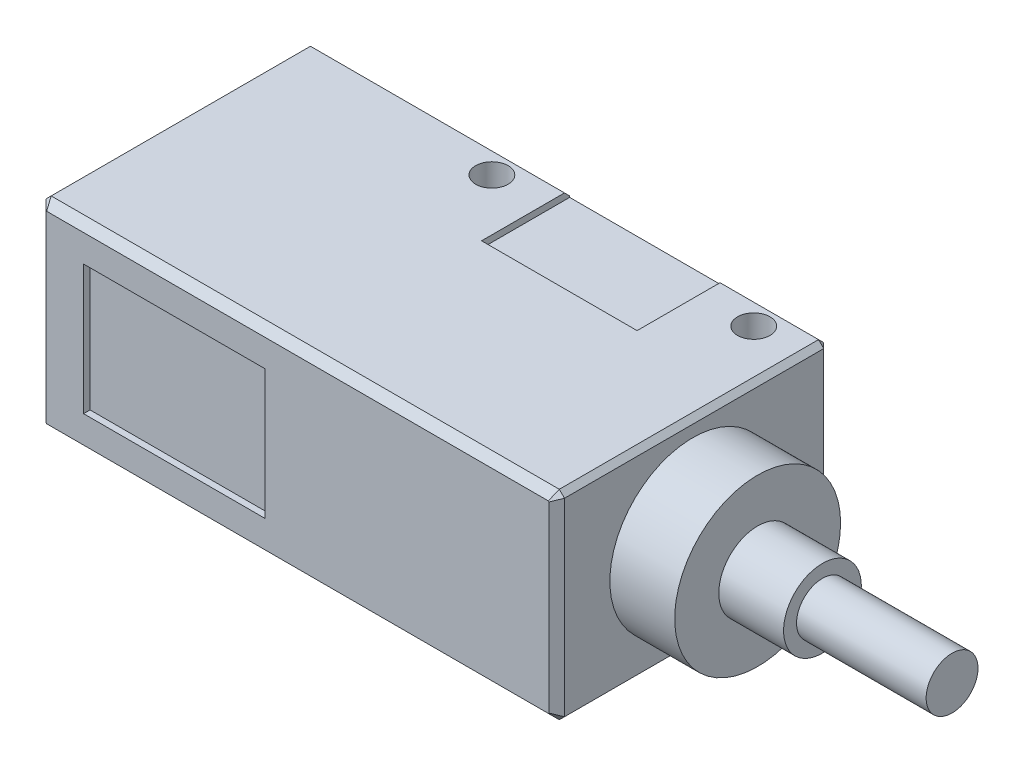
SolidWorks part; units mm, degrees
material "ABS"
ref_plane "Front Plane" through (0, 0, 0) normal (0, 0, 1) x (1, 0, 0)
ref_plane "Top Plane" through (0, 0, 0) normal (0, 1, 0) x (1, 0, 0)
ref_plane "Right Plane" through (0, 0, 0) normal (1, 0, 0) x (0, 0, -1)
sketch "Sketch1" plane through (0, 0, 0) normal (1, 0, 0) x (0, 0, -1)
  line L1 (-10.5, 7.7) -> (10.5, 7.7)
  line L2 (-10.5, 7.7) -> (-10.5, -7.7)
  line L3 (-10.5, -7.7) -> (10.5, -7.7)
  line L4 (10.5, 7.7) -> (10.5, -7.7)
  line L5 (-10.5, 7.7) -> (10.5, -7.7) construction
  line L6 (-10.5, -7.7) -> (10.5, 7.7) construction
  point P0 (0, 0)
  dimension "D1" = 21
  dimension "D2" = 15.4
extrude "Boss-Extrude1" add sketch "Sketch1" along normal blind 40
sketch "Sketch2" plane through (0, 0, 10.5) normal (0, 0, 1) x (1, 0, 0)
  line L0 (40, 7.7) -> (40, -7.7) construction
  line L1 (3.5, 5) -> (17.5, 5)
  line L2 (3.5, 5) -> (3.5, -5)
  line L3 (3.5, -5) -> (17.5, -5)
  line L4 (17.5, 5) -> (17.5, -5)
  line L5 (3.5, 5) -> (17.5, -5) construction
  line L6 (3.5, -5) -> (17.5, 5) construction
  line L10 (0, 0) -> (40, 0) construction
  point P0 (10.5, 0)
  dimension "D1" = 29.5
  dimension "D2" = 7
  dimension "D3" = 10
extrude "Cut-Extrude1" cut sketch "Sketch2" against normal blind 0.5
sketch "Sketch3" plane through (0, 7.7, 0) normal (0, 1, 0) x (1, 0, 0)
  line L0 (40, 10.5) -> (0, 10.5) construction
  line L1 (20, 10.5) -> (32, 10.5)
  line L2 (20, 10.5) -> (20, 3.7)
  line L3 (20, 3.7) -> (32, 3.7)
  line L4 (32, 10.5) -> (32, 3.7)
  line L5 (0, 10.5) -> (0, -10.5) construction
  dimension "D1" = 20
  dimension "D2" = 12
  dimension "D3" = 6.8
extrude "Cut-Extrude2" cut sketch "Sketch3" against normal blind 0.5
extrude "Cut-Extrude3" cut sketch "Sketch3<2>" along normal blind 0.5 from surface starting at face at (20, -7.7, 0)
sketch "Sketch3<2>" plane through (0, 7.7, 0) normal (0, 1, 0) x (1, 0, 0) same geometry as "Sketch3"
hole_wizard "M3 Tapped Hole1" positions "Sketch5" profile "Sketch4" tap size "M3" standard "ISO" end condition up to next
sketch "Sketch5" plane through (0, 7.7, 0) normal (0, 1, 0) x (-1, 0, 0)
  line L0 (-40, -10.5) -> (-32, -10.5) construction
  line L1 (-40, -10.5) -> (-40, 10.5) construction
  point P0 (-36.2, -8.5)
  dimension "D1" = 2
  dimension "D2" = 3.8
sketch "Sketch4" plane through (36.2, 7.7, -8.5) normal (1, 0, 0) x (0, 0, 1)
  line L0 (0, 0) -> (0, 15.4)
  line L1 (0, 15.4) -> (1.25, 15.4)
  line L2 (1.25, 15.4) -> (1.25, 0)
  line L5 (1.25, 0) -> (0, 0)
  line L11 (0, -6.35) -> (0, 107.95) construction
  dimension "Thru Tap Drill Dia." = 2.5
  dimension "Thru Tap Drill Depth" = 15.4
cosmetic thread "Hole Thread1" parameters "D2"=3
hole_wizard "M3 Tapped Hole2" positions "Sketch7" profile "Sketch6" tap size "M3" standard "ISO" end condition up to next
sketch "Sketch7" plane through (0, 7.7, 0) normal (0, 1, 0) x (-1, 0, 0)
  line L0 (-40, -10.5) -> (-40, 10.5) construction
  circle A0 centre (-36.2, -8.5) radius 1.25 construction
  point P0 (-16, -8.5)
  dimension "D1" = 0
  dimension "D2" = 24
sketch "Sketch6" plane through (16, 7.7, -8.5) normal (1, 0, 0) x (0, 0, 1)
  line L0 (0, 0) -> (0, 15.4)
  line L1 (0, 15.4) -> (1.25, 15.4)
  line L2 (1.25, 15.4) -> (1.25, 0)
  line L5 (1.25, 0) -> (0, 0)
  line L11 (0, -6.35) -> (0, 107.95) construction
  dimension "Thru Tap Drill Dia." = 2.5
  dimension "Thru Tap Drill Depth" = 15.4
cosmetic thread "Hole Thread2" parameters "D2"=3
sketch "Sketch8" plane through (40, 0, 0) normal (1, 0, 0) x (0, 0, -1)
  circle A0 centre (0, 0) radius 6.4
  dimension "D1" = 12.8
extrude "Boss-Extrude3" add sketch "Sketch8" along normal blind 5
sketch "Sketch9" plane through (45, 0, 0) normal (1, 0, 0) x (0, 0, -1)
  circle A0 centre (0, 0) radius 3
  dimension "D1" = 6
extrude "Boss-Extrude4" add sketch "Sketch9" along normal blind 5
sketch "Sketch10" plane through (50, 0, 0) normal (1, 0, 0) x (0, 0, -1)
  circle A0 centre (0, 0) radius 2
  dimension "D1" = 4
extrude "Boss-Extrude5" add sketch "Sketch10" along normal blind 10
chamfer "Chamfer1" distance 0.4 distance2 0.4 10 edges at (40, 7.7, 0) (36, 7.7, -10.5) (40, 0, -10.5) (40, -7.7, 0) (36, -7.7, -10.5) (0, 7.7, 0) (0, -7.7, 0) (10, 7.7, -10.5) (0, 0, -10.5) (10, -7.7, -10.5)
chamfer "Chamfer2" distance 0.6 distance2 0.6 8 edges at (39.8, 7.5, 10.5) (40, 0, 10.5) (39.8, -7.5, 10.5) (20, 7.7, 10.5) (0.2, 7.5, 10.5) (0, 0, 10.5) (0.2, -7.5, 10.5) (20, -7.7, 10.5)
